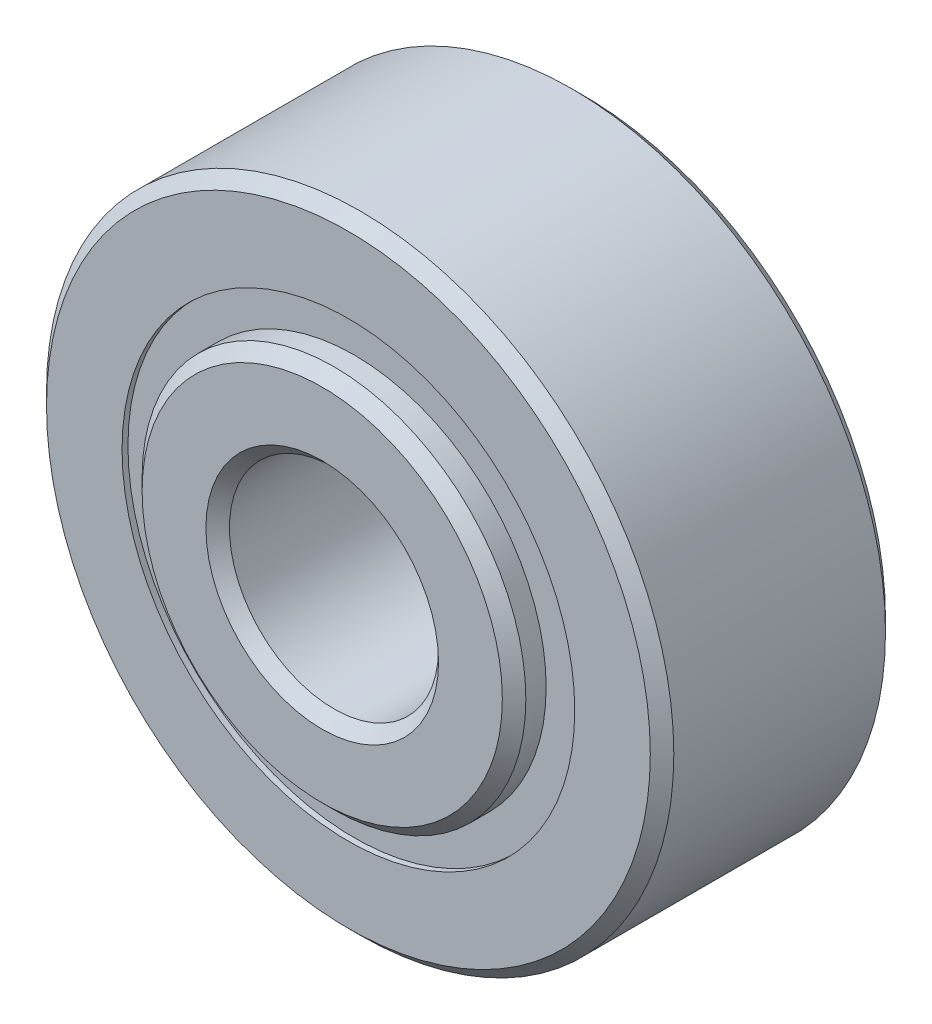
SolidWorks part; units mm, degrees
material "AISI 304"
ref_plane "Front Plane" through (0, 0, 0) normal (0, 0, 1) x (1, 0, 0)
ref_plane "Top Plane" through (0, 0, 0) normal (0, 1, 0) x (1, 0, 0)
ref_plane "Right Plane" through (0, 0, 0) normal (1, 0, 0) x (0, 0, -1)
sketch "Sketch1" plane through (0, 0, 0) normal (1, 0, 0) x (0, 0, -1)
  line L0 (-1.7856, 0) -> (1.7856, 0) construction
  line L1 (0, 4.7625) -> (0, -4.7625) construction
  line L2 (1.6071, 4.7625) -> (-1.6071, 4.7625)
  line L3 (-1.6071, 4.7625) -> (-1.7856, 4.5839)
  line L4 (-1.7856, 4.5839) -> (-1.7856, 3.4367)
  line L5 (-1.7856, 3.4367) -> (-0.7936, 3.4367)
  line L6 (1.7856, 3.4367) -> (0.7936, 3.4367)
  line L7 (1.7856, 4.5839) -> (1.7856, 3.4367)
  line L8 (1.6071, 4.7625) -> (1.7856, 4.5839)
  line L9 (0, 4.7625) -> (0, 3.175) construction
  line L10 (0, 3.175) -> (0, 1.5875) construction
  arc A0 (-0.7936, 3.4367) -> (0.7936, 3.4367) centre (0, 3.175) cw
  point P14 (0, 1.5875)
  dimension "D3" = 1.5872
  dimension "D1" = 45
  dimension "Width" = 3.5712
  dimension "OD" = 9.525
  dimension "D2" = 0.1786
  dimension "Shaft Dia" = 3.175
  dimension "D4" = 0.2617
revolve "Revolve1" add sketch "Sketch1" angle 360 about L0
sketch "Sketch3" plane through (0, 0, 0) normal (1, 0, 0) x (0, 0, -1)
  line L0 (-0.7936, 2.9133) -> (-2.1831, 2.9133) construction
  line L1 (-1.7856, 4.5839) -> (-1.7856, 3.4367) construction
  line L2 (-1.6071, 4.7625) -> (-1.7856, 4.5839) construction
  line L3 (-2.1831, 2.9133) -> (-2.1831, 1.7661) construction
  line L4 (-2.1831, 1.7661) -> (-2.1831, 2.7347)
  line L5 (-2.1831, 1.7661) -> (-2.0046, 1.5875)
  line L6 (-2.0046, 1.5875) -> (2.0046, 1.5875)
  line L8 (2.0046, 1.5875) -> (2.1831, 1.7661)
  line L10 (2.1831, 1.7661) -> (2.1831, 2.9133) construction
  line L11 (2.1831, 2.9133) -> (0.7936, 2.9133) construction
  line L12 (0, 4.7625) -> (0, -4.7625) construction
  line L13 (1.6071, 4.7625) -> (1.7856, 4.5839) construction
  line L14 (-2.1831, 2.7347) -> (-2.0046, 2.9133)
  line L15 (-2.0046, 2.9133) -> (-0.7936, 2.9133)
  line L16 (0.7936, 2.9133) -> (2.0046, 2.9133)
  line L17 (2.0046, 2.9133) -> (2.1831, 2.7347)
  line L18 (2.1831, 2.7347) -> (2.1831, 1.7661)
  arc A1 (0.7936, 2.9133) -> (-0.7936, 2.9133) centre (0, 3.175) cw
  arc A2 (0.7936, 3.4367) -> (-0.7936, 3.4367) centre (0, 3.175) ccw construction
  dimension "D1" = 45
  dimension "Ring" = 4.3663
revolve "Revolve3" add sketch "Sketch3" angle 360 about L0
sketch "Sketch4" plane through (0, 0, 0) normal (1, 0, 0) x (0, 0, -1)
  line L0 (-0.8356, 3.175) -> (0.8356, 3.175)
  arc A2 (-0.8356, 3.175) -> (0.8356, 3.175) centre (0, 3.175) cw
  arc A3 (0.7936, 3.4367) -> (-0.7936, 3.4367) centre (0, 3.175) ccw construction
revolve "Revolve4" add sketch "Sketch4" angle 360 about L0
ref_axis "Axis1" through (0, 0, -1.7856) along (0, 0, 1)
pattern_circular "CirPattern1" count 10 every 36 about axis through (0, 0, -1.7856) along (0, 0, 1) of bodies 104
sketch "Sketch5" plane through (0, 0, 0) normal (1, 0, 0) x (0, 0, -1)
  line L0 (-1.7856, 3.4367) -> (-0.7936, 3.4367) construction
  line L1 (-1.6963, 3.4367) -> (-0.8356, 3.4367)
  line L2 (-1.6963, 3.4367) -> (-1.6963, 2.9133)
  line L3 (-1.6963, 2.9133) -> (-0.8356, 2.9133)
  line L4 (-0.8356, 3.4367) -> (-0.8356, 2.9133)
  line L5 (-0.7936, 2.9133) -> (-2.1831, 2.9133) construction
  line L6 (1.7856, 3.4367) -> (0.7936, 3.4367) construction
  line L7 (1.6963, 3.4367) -> (0.8356, 3.4367)
  line L8 (1.6963, 3.4367) -> (1.6963, 2.9133)
  line L9 (1.6963, 2.9133) -> (0.8356, 2.9133)
  line L10 (0.8356, 3.4367) -> (0.8356, 2.9133)
  line L11 (2.1831, 2.9133) -> (0.7936, 2.9133) construction
  line L12 (-1.6071, 4.7625) -> (-1.7856, 4.5839) construction
  point P18 (-1.6963, 4.6732)
revolve "Revolve5" add sketch "Sketch5" angle 360 about L0
equation "\"D2@Sketch1\" = \"Width@Sketch1\"*.05"
equation "\"D3@Sketch1\" = \"Width@Sketch1\"/2.25"
equation "\"D4@Sketch1\" = (((\"OD@Sketch1\"-\"Width@Sketch1\")/2)/3.25)/3.5"
equation "\"D2@CirPattern1\" = 360/\"Balls@CirPattern1\""
